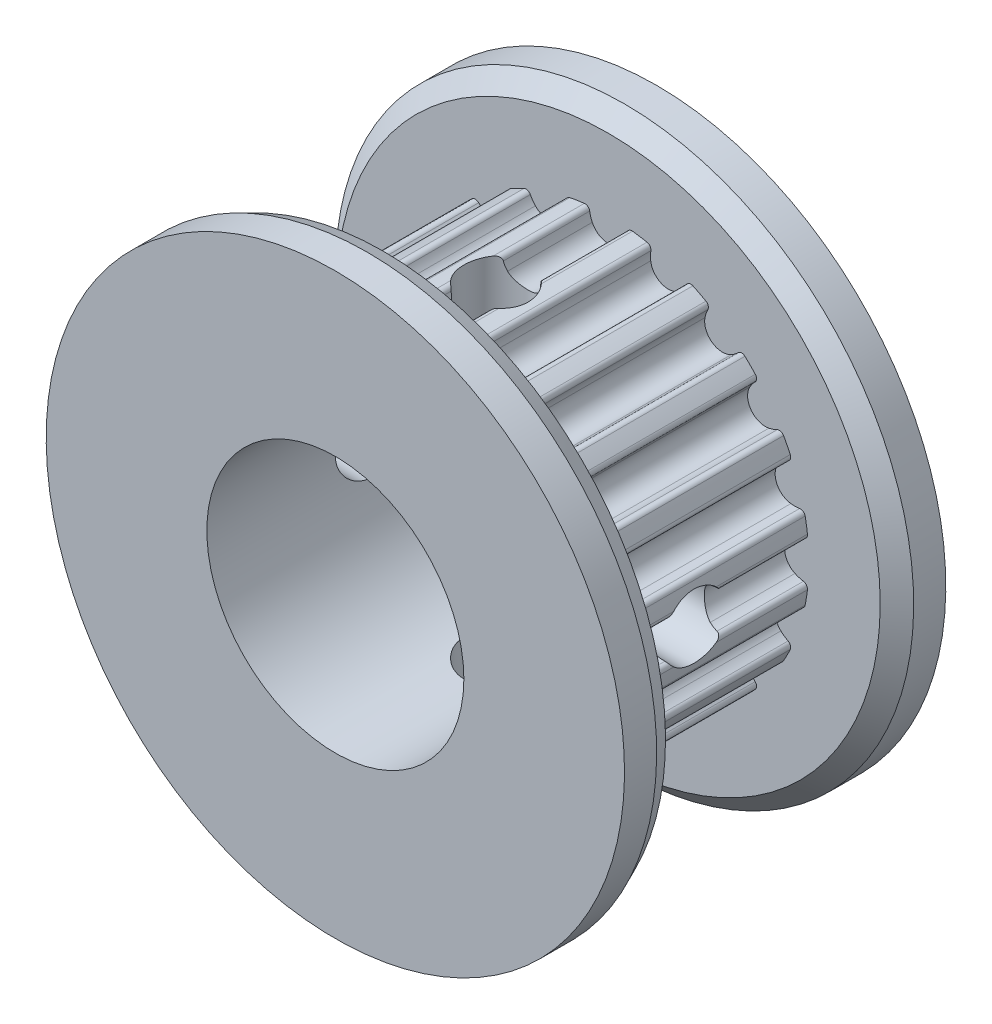
SolidWorks part; units mm, degrees
material "Aleación 6061"
ref_plane "Alzado" through (0, 0, 0) normal (0, 0, 1) x (1, 0, 0)
ref_plane "Planta" through (0, 0, 0) normal (0, 1, 0) x (1, 0, 0)
ref_plane "Vista lateral" through (0, 0, 0) normal (1, 0, 0) x (0, 0, -1)
sketch "Croquis1" plane through (0, 0, 0) normal (0, 0, 1) x (1, 0, 0)
  circle A0 centre (0, 0) radius 6.366
  dimension "D1" = 12.732
extrude "Saliente-Extruir1" add sketch "Croquis1" along normal blind 7
sketch "Croquis3" plane through (0, 0, 0) normal (0, 0, -1) x (-1, 0, 0)
  line L0 (0, 0) -> (0, 6.239) construction
  line L1 (0, 0) -> (0.976, 6.1622) construction
  line L2 (0.976, 6.1622) -> (0, 0) construction
  line L3 (0, 0) -> (-0.976, 6.1622) construction
  line L6 (0.976, 6.1622) -> (0.9959, 6.2876)
  line L8 (-0.976, 6.1622) -> (-0.9959, 6.2876)
  arc A0 (-0.7498, 6.1938) -> (-0.976, 6.1622) centre (0, 0) ccw
  arc A1 (-0.5037, 5.8059) -> (0.5037, 5.8059) centre (0, 6.039) ccw
  arc A2 (-0.5837, 6.0685) -> (-0.5037, 5.8059) centre (0.4038, 6.2259) ccw
  arc A3 (-0.5837, 6.0685) -> (-0.7498, 6.1938) centre (-0.7318, 6.0449) ccw
  arc A4 (0.5837, 6.0685) -> (0.5037, 5.8059) centre (-0.4038, 6.2259) cw
  arc A5 (0.5837, 6.0685) -> (0.7498, 6.1938) centre (0.7318, 6.0449) cw
  arc A6 (0.7498, 6.1938) -> (0.976, 6.1622) centre (0, 0) cw
  circle A7 centre (0, 0) radius 6.366 construction
  circle A11 centre (0, 0) radius 6.366
  circle M8 centre (0, 0) radius 6.366
  dimension "D1" = 6.239
  dimension "D4" = 1.11
  dimension "D5" = 2
  dimension "D7" = 0.3
  dimension "D3" = 18
  dimension "D6" = 0.2
extrude "Cortar-Extruir1" cut sketch "Croquis3" against normal through all contours A5 A6 L6 L8 A0 A3 A2 A1 A4 M8 region at (0, 6.0066, 0)
pattern_circular "MatrizC1" count 20 over 360 about axis through (0, 0, 7) along (0, 0, -1) of "Cortar-Extruir1"
sketch "Croquis5" plane through (0, 0, 0) normal (1, 0, 0) x (0, 0, -1)
  line L0 (0, 0) -> (1.5, 0)
  line L1 (0, -0.5037) -> (0, 0.5037) construction
  line L2 (1.5, 0) -> (1.5, 9)
  line L4 (0, 8.4583) -> (0, 0)
  line L5 (-7, 0) -> (-8.5, 0)
  line L6 (-7, 0.5037) -> (-7, -0.5037) construction
  line L7 (-8.5, 0) -> (-8.5, 9)
  line L10 (-7, 0) -> (-7, 8.776)
  line L11 (-8.5, 9) -> (-7.5, 9)
  line L12 (-7.5, 9) -> (-7, 8.776)
  line L13 (1.5, 9) -> (0.5, 9)
  line L14 (0.5, 9) -> (0, 8.4583)
  dimension "D1" = 9
  dimension "D2" = 1
  dimension "D3" = 9
  dimension "D4" = 0.5
  dimension "D5" = 1
  dimension "D6" = 0.5
revolve "Revolución1" add sketch "Croquis5" angle 360 about L5
sketch "Croquis6" plane through (0, 0, 8.5) normal (0, 0, 1) x (1, 0, 0)
  circle A0 centre (0, 0) radius 4
  dimension "D1" = 8
extrude "Cortar-Extruir2" cut sketch "Croquis6" against normal through all
sketch "Croquis7" plane through (0, 0, 0) normal (1, 0, 0) x (0, 0, -1)
  circle A0 centre (-3.5, 0) radius 1
  dimension "D1" = 2
extrude "Cortar-Extruir3" cut sketch "Croquis7" against normal through all both and the other way through all
sketch "Croquis8" plane through (0, 0, 0) normal (0, 1, 0) x (1, 0, 0)
  line L0 (0, 1.5) -> (0, -8.5) construction
  line L1 (9, 1.5) -> (-9, 1.5) construction
  line L2 (-4, -8.5) -> (4, -8.5) construction
  circle A1 centre (0, -3.5) radius 1
  dimension "D1" = 2
extrude "Cortar-Extruir4" cut sketch "Croquis8" against normal through all both and the other way through all
